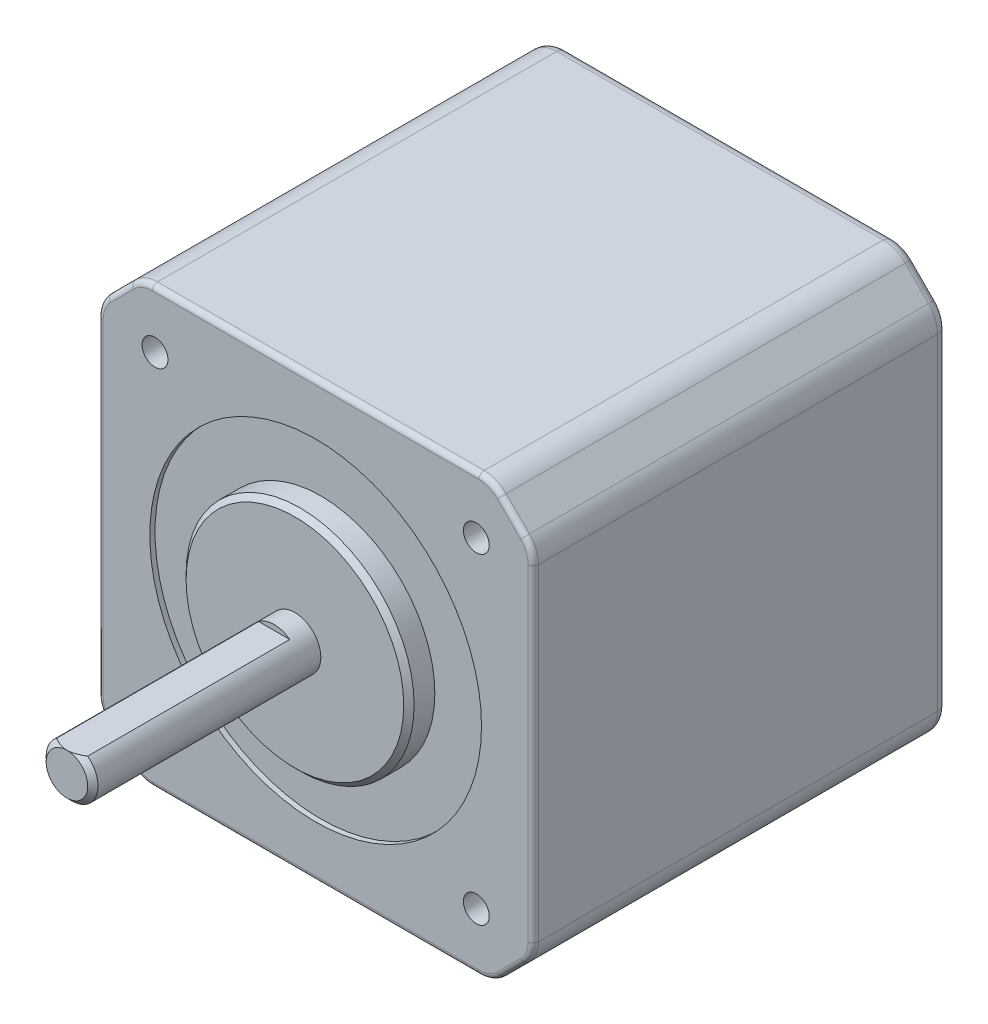
SolidWorks part; units mm, degrees
material "Commercially Pure CP-Ti UNS R50400 (SS)"
ref_plane "Front Plane" through (0, 0, 0) normal (0, 0, 1) x (1, 0, 0)
ref_plane "Top Plane" through (0, 0, 0) normal (0, 1, 0) x (1, 0, 0)
ref_plane "Right Plane" through (0, 0, 0) normal (1, 0, 0) x (0, 0, -1)
sketch "Sketch1" plane through (0, 0, 0) normal (0, 0, 1) x (1, 0, 0)
  line L1 (-21, -21) -> (21, -21)
  line L2 (-21, -21) -> (-21, 21)
  line L3 (-21, 21) -> (21, 21)
  line L4 (21, -21) -> (21, 21)
  line L5 (-21, -21) -> (21, 21) construction
  line L6 (-21, 21) -> (21, -21) construction
  point P0 (0, 0)
  dimension "D1" = 42
  dimension "D2" = 42
extrude "Boss-Extrude1" add sketch "Sketch1" along normal mid plane 40
chamfer "Chamfer1" distance 4 angle 45 4 edges at (-21, -21, 0) (21, -21, 0) (-21, 21, 0) (21, 21, 0)
sketch "Sketch2" plane through (0, 0, 20) normal (0, 0, 1) x (1, 0, 0)
  circle A0 centre (0, 0) radius 11
  dimension "D1" = 22
extrude "Boss-Extrude2" add sketch "Sketch2" along normal blind 2
sketch "Sketch3" plane through (0, 0, 20) normal (0, 0, 1) x (1, 0, 0)
  circle A0 centre (0, 0) radius 16
  circle A1 centre (0, 0) radius 11
  dimension "D1" = 32
extrude "Cut-Extrude1" cut sketch "Sketch3" against normal blind 0.5
sketch "Sketch4" plane through (0, 0, 22) normal (0, 0, 1) x (1, 0, 0)
  circle A0 centre (0, 0) radius 2.5
  dimension "D1" = 5
extrude "Boss-Extrude3" add sketch "Sketch4" along normal blind 22
sketch "Sketch5" plane through (0, 0, 44) normal (0, 0, 1) x (1, 0, 0)
  line L1 (-4.4436, 2) -> (5.9206, 2)
  line L2 (-4.4436, 2) -> (-4.4436, 3.526)
  line L3 (-4.4436, 3.526) -> (5.9206, 3.526)
  line L4 (5.9206, 2) -> (5.9206, 3.526)
  dimension "D1" = 2
extrude "Cut-Extrude2" cut sketch "Sketch5" against normal blind 20
hole_wizard "M3x0.5 Tapped Hole1" positions "Sketch6" profile "Sketch7" tap size "M3x0.5" standard "ANSI Metric"
sketch "Sketch6" plane through (0, 0, 20) normal (0, 0, 1) x (1, 0, 0)
  point P0 (-15.5, 15.5)
  dimension "D1" = 15.5
  dimension "D2" = 15.5
sketch "Sketch7" plane through (-15.5, 15.5, 20) normal (1, 0, 0) x (0, -1, 0)
  line L0 (0, 0) -> (0, 8.2511)
  line L1 (0, 8.2511) -> (1.25, 7.5)
  line L2 (1.25, 7.5) -> (1.25, 0)
  line L5 (1.25, 0) -> (0, 0)
  line L10 (0, 8.2511) -> (-1.25, 7.5) construction
  line L11 (0, -6.35) -> (0, 107.95) construction
  dimension "Tap Drill Dia." = 2.5
  dimension "Tap Drill Depth" = 7.5
  dimension "Drill Angle" = 118
cosmetic thread "Hole Thread1" parameters "D1"=6, "D2"=3
pattern_circular "CirPattern1" count 4 over 360 about axis through (0, 0, 22) along (0, 0, -1) of "M3x0.5 Tapped Hole1"
fillet "Fillet1" radius 3 8 edges at (-21, -17, 0) (-17, -21, 0) (17, -21, 0) (21, -17, 0) (21, 17, 0) (17, 21, 0) (-21, 17, 0) (-17, 21, 0)
chamfer "Chamfer2" distance 0.5 angle 45 2 edges at (0, -2.5, 44) (11, 0, 22)
fillet "Fillet2" radius 1 16 edges at (16.9054, 20.7716, -20) (19, 19, -20) (20.7716, 16.9054, -20) (21, 0, -20) (20.7716, -16.9054, -20) (19, -19, -20) (16.9054, -20.7716, -20) (0, -21, -20) (-16.9054, -20.7716, -20) (-19, -19, -20) (-20.7716, -16.9054, -20) (-21, 0, -20) (-20.7716, 16.9054, -20) (-19, 19, -20) (-16.9054, 20.7716, -20) (0, 21, -20)
fillet "Fillet3" radius 0.5 16 edges at (16.9054, 20.7716, 20) (19, 19, 20) (20.7716, 16.9054, 20) (21, 0, 20) (20.7716, -16.9054, 20) (19, -19, 20) (16.9054, -20.7716, 20) (0, -21, 20) (-16.9054, -20.7716, 20) (-19, -19, 20) (-20.7716, -16.9054, 20) (-21, 0, 20) (-20.7716, 16.9054, 20) (-19, 19, 20) (-16.9054, 20.7716, 20) (0, 21, 20)
sketch "Sketch8" plane through (0, -21, 0) normal (0, -1, 0) x (1, 0, 0)
  circle A1 centre (0, -18.5744) radius 0.65
  circle A2 centre (1.1585, -19.5) radius 0.65
  circle A3 centre (0.0324, -20.3521) radius 0.65
  circle A4 centre (-1.1368, -19.5) radius 0.65
  dimension "D3" = 1.3
  dimension "D4" = 1.3
  dimension "D5" = 1.3
  dimension "D6" = 1.3
extrude "Boss-Extrude4" add sketch "Sketch8" along normal blind 2
sketch "Sketch9" plane through (0, 0, -20) normal (0, 0, -1) x (-1, 0, 0)
  circle A0 centre (0, 0) radius 3.5
  dimension "D1" = 7
extrude "Cut-Extrude3" cut sketch "Sketch9" against normal blind 3.5
